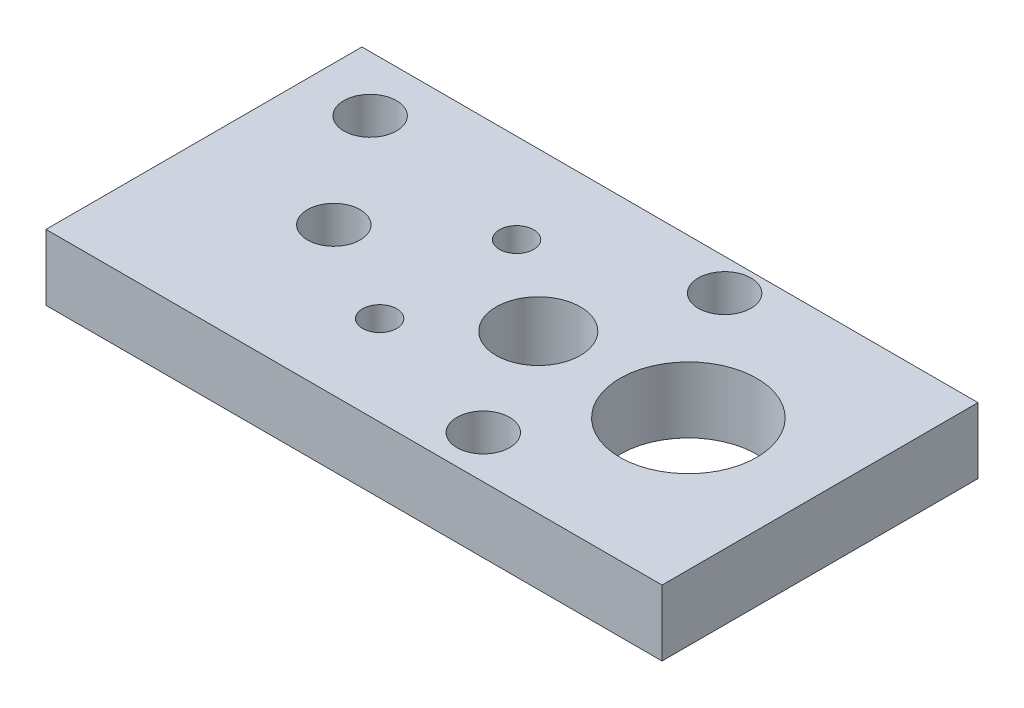
SolidWorks part; units mm, degrees
ref_plane "前视基准面" through (0, 0, 0) normal (0, 0, 1) x (1, 0, 0)
ref_plane "上视基准面" through (0, 0, 0) normal (0, 1, 0) x (1, 0, 0)
ref_plane "右视基准面" through (0, 0, 0) normal (1, 0, 0) x (0, 0, -1)
other "Configuration Table"
sketch "草图1" plane through (0, 0, 0) normal (0, 1, 0) x (1, 0, 0)
  line L0 (5.0509, -6) -> (27.896, -6) construction
  line L1 (0, 0) -> (23.3957, 0)
  line L2 (0, 0) -> (0, -12)
  line L3 (0, -12) -> (23.3957, -12)
  line L4 (23.3957, 0) -> (23.3957, -12)
  line L5 (9.2708, -3.4) -> (9.2708, -8.6) construction
  circle A2 centre (9.2708, -3.4) radius 0.65
  circle A3 centre (12.6957, -6) radius 1.6
  circle A4 centre (9.2708, -8.6) radius 0.65
  circle A5 centre (18.3957, -6) radius 2.6
  point P5 (5, -6)
  point P16 (9.2708, -6)
  point P17 (13.1579, -10)
  dimension "D4" = 1.3
  dimension "D6" = 3.2
  dimension "D8" = 5.7
  dimension "D11" = 5.2
  dimension "D1" = 6
  dimension "D2" = 5
  dimension "D3" = 5
  dimension "D5" = 5.2
  dimension "D7" = 5
  dimension "D9" = 4.3
  dimension "D12" = 12
extrude "凸台-拉伸1" add sketch "草图1" along normal blind 2.5 contours L4 L3 L2 L1 | A2 | A3 | A4 | A5
sketch "草图3" plane through (0, 2.5, 0) normal (0, 1, 0) x (1, 0, 0)
  circle A0 centre (2.4192, -2.1089) radius 1
  circle A1 centre (5.3147, -6.3844) radius 1
  circle A2 centre (14.9835, -1.2099) radius 1
  circle A3 centre (14.9835, -10.3761) radius 1
  circle A4 centre (5.3147, -6.3844) radius 0.7
  circle A5 centre (2.4192, -2.1089) radius 0.7
  circle A6 centre (14.9835, -1.2099) radius 0.7
  circle A7 centre (14.9835, -10.3761) radius 0.7
  point P12 (0, 0)
  point P13 (0, 0)
  point P14 (0, 0)
  point P15 (0, 0)
  point P16 (0, 0)
  point P17 (0, 0)
  dimension "D1" = 1.4
  dimension "D2" = 2
extrude "切除-拉伸1" cut sketch "草图3" against normal through all contours A5 | A4 | A6 | A7
extrude "切除-拉伸2" cut sketch "草图3<3>" against normal blind 1.5 contours A0 | A1 | A3 | A2
sketch "草图3<3>" plane through (0, 2.5, 0) normal (0, 1, 0) x (1, 0, 0) same geometry as "草图3"
